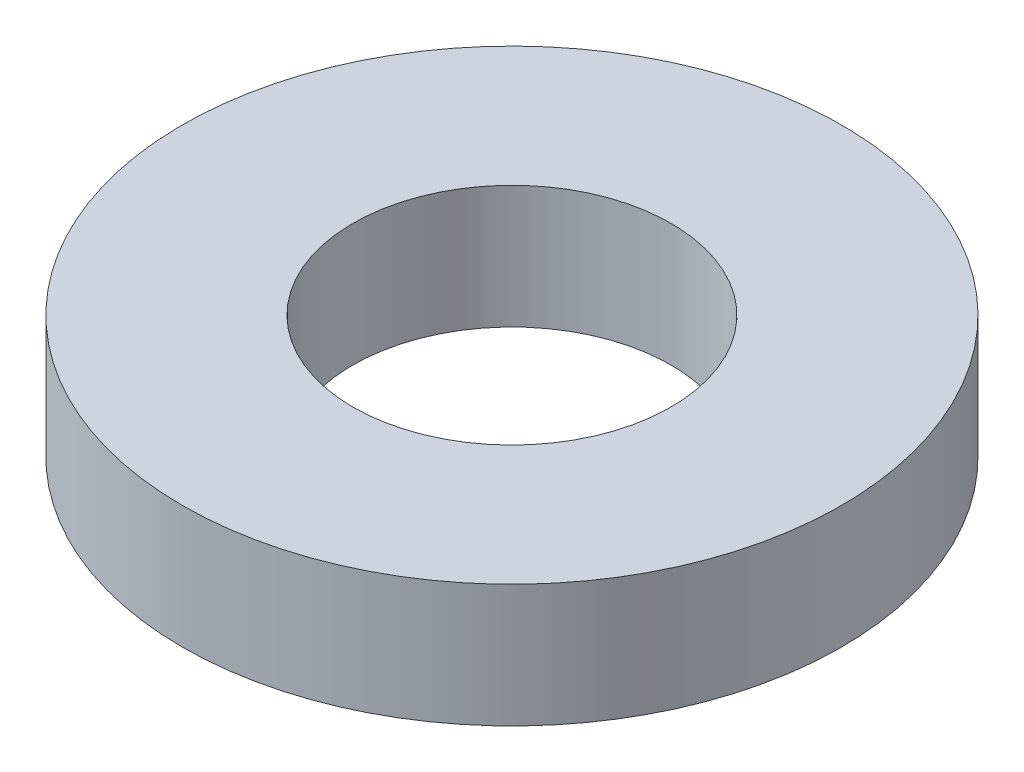
SolidWorks part; units mm, degrees
ref_plane "Front Plane" through (0, 0, 0) normal (0, 0, 1) x (1, 0, 0)
ref_plane "Top Plane" through (0, 0, 0) normal (0, 1, 0) x (1, 0, 0)
ref_plane "Right Plane" through (0, 0, 0) normal (1, 0, 0) x (0, 0, -1)
sketch "Sketch1" plane through (0, 0, 0) normal (0, 1, 0) x (1, 0, 0)
  circle A0 centre (0, 0) radius 72.5
  dimension "FLANGE_OD" = 145
extrude "Boss-Extrude1" add sketch "Sketch1" along normal blind 27
sketch "Sketch2" plane through (0, 0, 0) normal (0, 1, 0) x (1, 0, 0)
  circle A0 centre (0, 0) radius 35
  dimension "BORE_D" = 70
extrude "Cut-Extrude1" cut sketch "Sketch2" along normal through all
sketch "Sketch3" plane through (0, 27, 0) normal (0, 1, 0) x (1, 0, 0)
  circle A0 centre (0, 0) radius 25.2423 construction
  circle A1 centre (-25.2423, 0) radius 6.5656
  dimension "BOLT_D" = 13.1312
  dimension "BOLT_PCD" = 50.4846
extrude "Cut-Extrude2" cut sketch "Sketch3" against normal blind 17.5623 rebuild error yes
pattern_circular "CirPattern1" count 8 over 360 rebuild error yes
